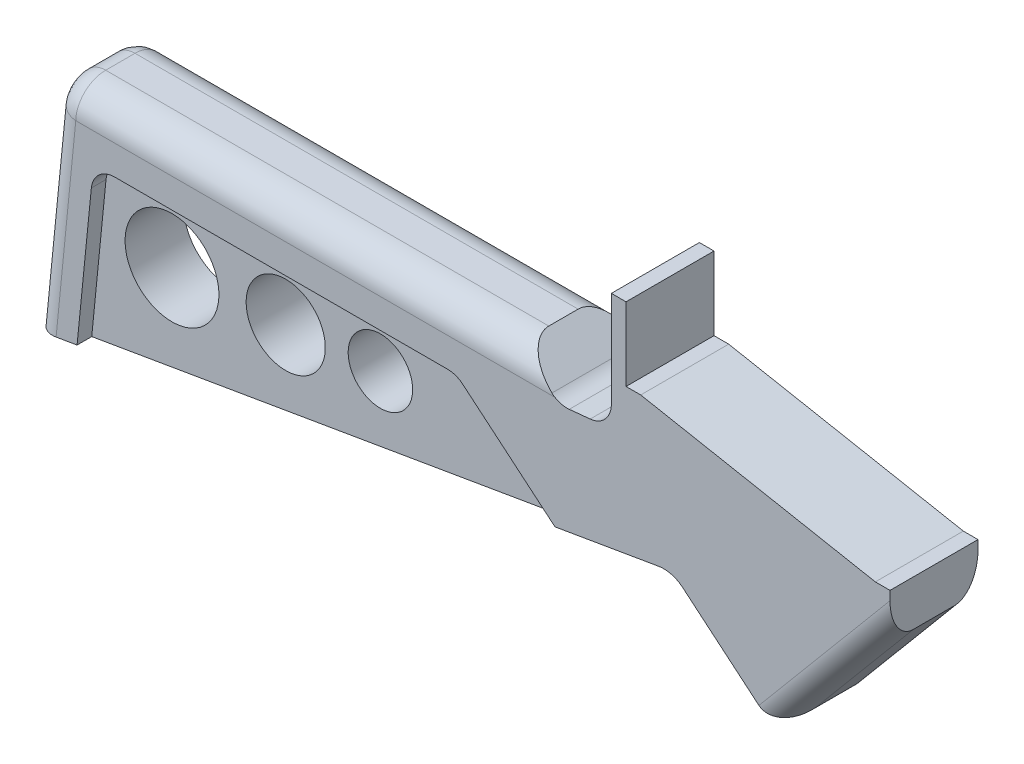
SolidWorks part; units mm, degrees
ref_plane "Front Plane" through (0, 0, 0) normal (0, 0, 1) x (1, 0, 0)
ref_plane "Top Plane" through (0, 0, 0) normal (0, 1, 0) x (1, 0, 0)
ref_plane "Right Plane" through (0, 0, 0) normal (1, 0, 0) x (0, 0, -1)
sketch "Sketch1" plane through (0, 0, 0) normal (0, 0, 1) x (1, 0, 0)
  line L0 (0, 0) -> (85, 0) construction
  line L1 (0, 0) -> (0, 15.5) construction
  line L2 (0, 15.5) -> (85, 15.5) construction
  line L3 (85, 15.5) -> (85, 0)
  line L4 (80, 15.5) -> (0, 30.6972)
  line L5 (0, 30.6972) -> (-5, 30.6972)
  line L6 (-5, 30.6972) -> (-5, 55.6972)
  line L7 (-5, 55.6972) -> (-10, 55.6972)
  line L8 (-10, 55.6972) -> (-10, 15.6972)
  line L9 (85, 0) -> (46.4327, -45.9627)
  line L10 (46.4327, -45.9627) -> (10.774, -16.0415)
  line L11 (10.774, -16.0415) -> (-207.4926, -53.2717)
  line L12 (-207.4926, -53.2717) -> (-199.651, 25.3735)
  line L15 (80, 15.5) -> (85, 15.5)
  line L16 (-199.651, 25.3735) -> (-41.3345, 25.3735)
  line L17 (-41.3345, 25.3735) -> (-27.713, 13.9437)
  line L18 (-27.713, 13.9437) -> (-10, 15.6972)
  dimension "D1" = 85
  dimension "D2" = 15.5
  dimension "D3" = 5
  dimension "D4" = 5
  dimension "D5" = 10.756
  dimension "D6" = 50
  dimension "D7" = 60
  dimension "D8" = 5
  dimension "D9" = 80
  dimension "D10" = 40
  dimension "D11" = 25
extrude "Boss-Extrude1" add sketch "Sketch1" along normal blind 15 contours L3 L9 L10 L11 L12 L16 L17 L18 L8 L7 L6 L5 L4 L15
sketch "Sketch2" plane through (0, 0, 0) normal (0, 0, 1) x (1, 0, 0)
  line L0 (10.774, -16.0415) -> (-29.226, -22.8644) construction
  line L1 (10.774, -16.0415) -> (-207.4926, -53.2717) construction
  line L2 (-29.226, -22.8644) -> (-62.8785, 5.3735)
  line L3 (-62.8785, 5.3735) -> (-186.5708, 5.3735)
  line L4 (-186.5708, 5.3735) -> (-192.1574, -50.6559)
  line L5 (-207.4926, -53.2717) -> (-199.651, 25.3735) construction
  line L6 (-199.651, 25.3735) -> (-41.3345, 25.3735) construction
  line L7 (-41.3345, 25.3735) -> (-27.713, 13.9437) construction
  line L8 (-192.1574, -50.6559) -> (-29.226, -22.8644)
  dimension "D1" = 40
  dimension "D2" = 15
  dimension "D3" = 20
extrude "Cut-Extrude1" cut sketch "Sketch2" along normal blind 5
fillet "Fillet1" radius 10 2 edges at (-120.4927, 25.3735, 0) (10.774, -16.0415, 7.5)
fillet "Fillet2" radius 8 9 edges at (-199.651, 25.3735, 12.5) (-199.943, 22.4445, 2.9289) (-204.0703, -18.9491, 0) (65.7164, -22.9813, 0) (46.4327, -45.9627, 7.5) (-186.5708, 5.3735, 2.5) (-62.8785, 5.3735, 2.5) (-10, 15.6972, 7.5) (-27.713, 13.9437, 7.5)
sketch "Sketch3" plane through (0, 0, 5) normal (0, 0, -1) x (-1, 0, 0)
  line L0 (73.9846, -0.6265) -> (179.1682, -0.6265) construction
  line L1 (65.7902, 5.3735) -> (179.3288, 5.3735) construction
  line L2 (65.7902, 5.3735) -> (179.3288, 5.3735) construction
  circle A0 centre (93.7405, -11.6265) radius 11
  circle A1 centre (164.801, -16.6265) radius 16
  circle A2 centre (126.0265, -14.1265) radius 13.5
  dimension "D2" = 22
  dimension "D3" = 32
  dimension "D4" = 27
  dimension "D1" = 6
extrude "Cut-Extrude2" cut sketch "Sketch3" against normal through all
mirror "Mirror1" about plane through (0, 0, 15) normal (0, 0, -1) of bodies 104 102
